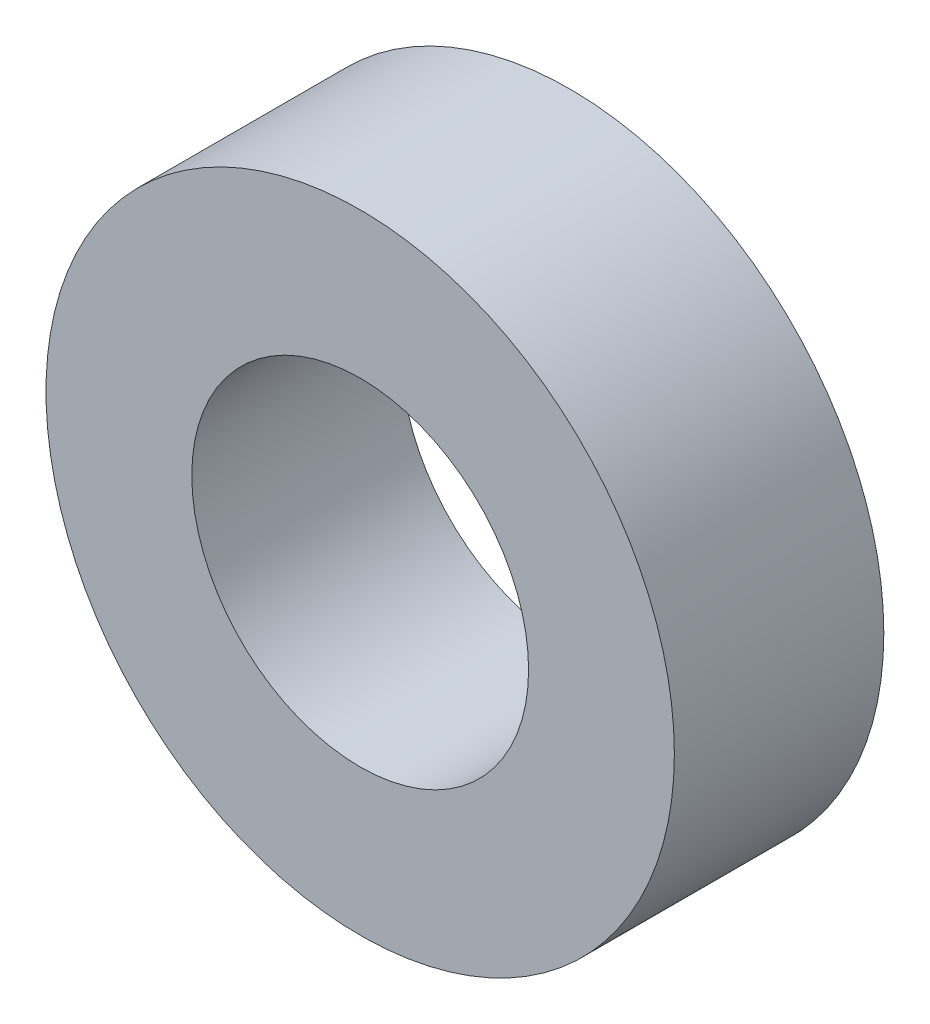
SolidWorks part; units mm, degrees
ref_plane "Front Plane" through (0, 0, 0) normal (0, 0, 1) x (1, 0, 0)
ref_plane "Top Plane" through (0, 0, 0) normal (0, 1, 0) x (1, 0, 0)
ref_plane "Right Plane" through (0, 0, 0) normal (1, 0, 0) x (0, 0, -1)
sketch "Sketch1" plane through (0, 0, 0) normal (0, 0, 1) x (1, 0, 0)
  circle A0 centre (0, 0) radius 4.7625
  circle A1 centre (0, 0) radius 2.5527
  dimension "D1" = 9.525
  dimension "D2" = 5.1054
extrude "Boss-Extrude1" add sketch "Sketch1" along normal mid plane 3.175
